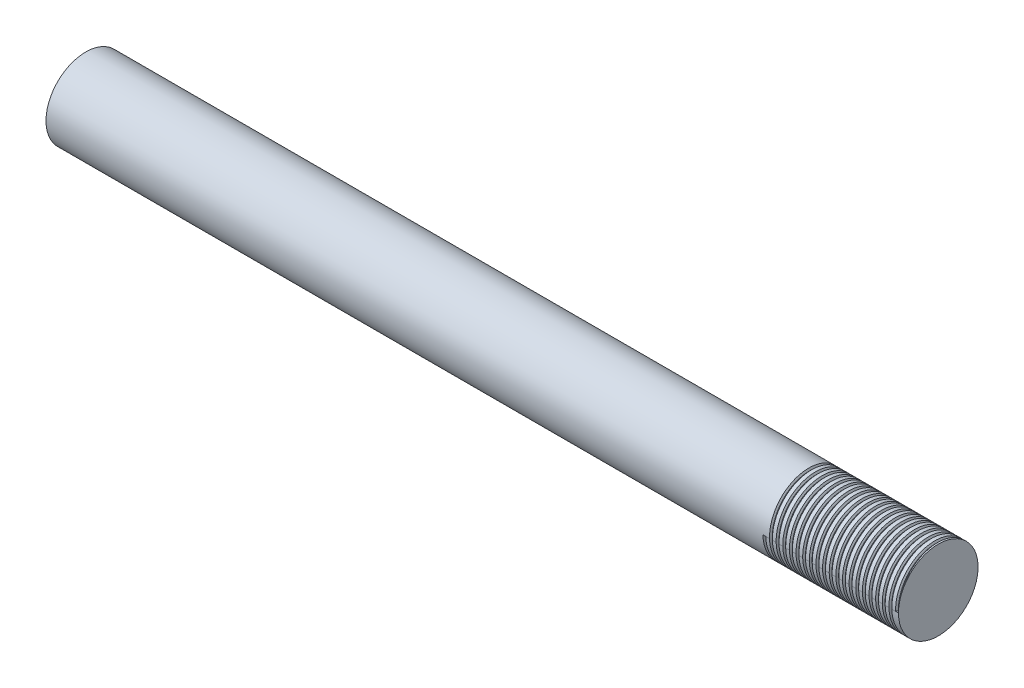
SolidWorks part; units mm, degrees
ref_plane "Ebene vorne" through (0, 0, 0) normal (0, 0, 1) x (1, 0, 0)
ref_plane "Ebene oben" through (0, 0, 0) normal (0, 1, 0) x (1, 0, 0)
ref_plane "Ebene rechts" through (0, 0, 0) normal (1, 0, 0) x (0, 0, -1)
sketch "Skizze2" plane through (0, 0, 0) normal (0, 0, 1) x (1, 0, 0)
  line L0 (0, 0) -> (77.9436, 0) construction
  line L1 (0, 0) -> (0, 3)
  line L2 (0, 3) -> (64.25, 3)
  line L3 (64.25, 3) -> (64.25, 0)
  line L4 (0, 0) -> (64.25, 0)
  dimension "D1" = 3
  dimension "D2" = 64.25
revolve "Rotation1" add sketch "Skizze2" angle 360 about L0
thread "Gewinde1" pitch 0.25 method cut profile "Gewindeprofil2" start angle 0, offset 0, length 10, pitch 0.5, diameter 6
ref_plane "Ebene2" through (64.25, 0, 3) normal (0, -1, 0) x (0, 0, 1)
sketch "Gewindeprofil2" plane through (64.25, 0, 3) normal (0, -1, 0) x (0, 0, 1)
  line L0 (0, 0) -> (0, 0.25) construction
  line L11 (0, 0) -> (0, 0.2187)
  line L12 (0, 0.2187) -> (-0.1353, 0.1406)
  line L13 (-0.1353, 0.1406) -> (-0.1353, 0.0781)
  line L15 (-0.1353, 0.0781) -> (0, 0)
  line L17 (-0.1353, 0.1094) -> (0, 0.1094) construction
  point P2 (0, 0)
  dimension "Pitch" = 0.25
  dimension "Profile_Angle" = 60
  dimension "Profile_Land" = 0.0625
  dimension "Profile_Height" = 0.1353
